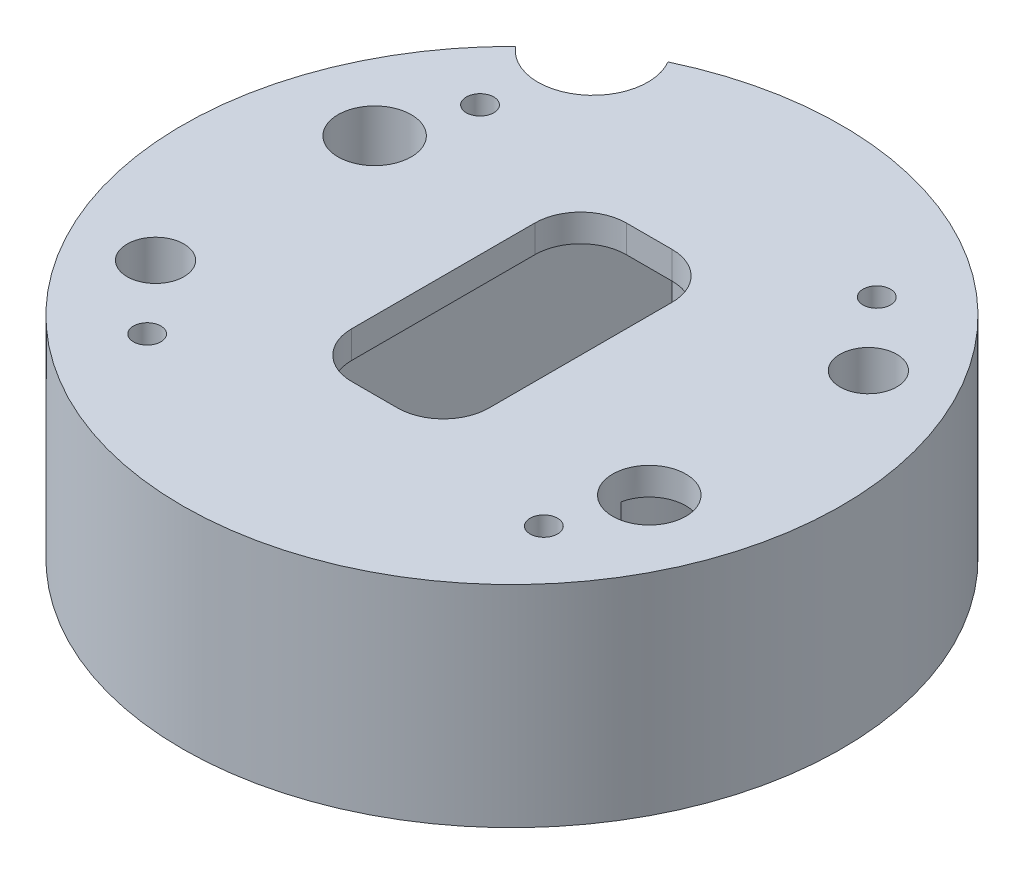
SolidWorks part; units mm, degrees
ref_plane "Front Plane" through (0, 0, 0) normal (0, 0, 1) x (1, 0, 0)
ref_plane "Top Plane" through (0, 0, 0) normal (0, 1, 0) x (1, 0, 0)
ref_plane "Right Plane" through (0, 0, 0) normal (1, 0, 0) x (0, 0, -1)
sketch "Sketch1" plane through (0, 0, 0) normal (0, 1, 0) x (1, 0, 0)
  line L0 (-13, 30.5) -> (13, -30.5) construction
  line L1 (-13, 30.5) -> (13, 30.5)
  line L2 (-13, 30.5) -> (-13, -30.5)
  line L3 (-13, -30.5) -> (13, -30.5)
  line L4 (13, 30.5) -> (13, -30.5)
  line L5 (-24.5, 0) -> (24.5, 0) construction
  line L6 (-34, 0) -> (-36, 0) construction
  line L7 (34, 0) -> (36, 0) construction
  line L8 (-15, 0) -> (-13, 0) construction
  circle A0 centre (0, 0) radius 36
  circle A3 centre (-24.5, 0) radius 9.5
  circle A4 centre (24.5, 0) radius 9.5
  point P5 (0, 0)
  point P12 (0, 0)
  dimension "D1" = 72
  dimension "D2" = 61
  dimension "D4" = 19
  dimension "D3" = 26
extrude "Boss-Extrude1" add sketch "Sketch1" along normal blind 20
sketch "Sketch4" plane through (0, 20, 0) normal (0, 1, 0) x (1, 0, 0)
  line L0 (-24.5, 9.5) -> (-24.5, 0) construction
  line L1 (-24.5, 0) -> (24.5, 0) construction
  line L2 (24.5, 0) -> (24.5, -9.5) construction
  line L3 (-24.5, 9.5) -> (-1.5428, 9.5) construction
  circle A0 centre (-24.5, 9.5) radius 4
  circle A1 centre (-24.5, 0) radius 9.5 construction
  circle A3 centre (24.5, -9.5) radius 4
  circle A5 centre (24.5, 0) radius 9.5 construction
  dimension "D1" = 8
extrude "Cut-Extrude6" cut sketch "Sketch4" against normal through all
sketch "Sketch5" plane through (0, 20, 0) normal (0, 1, 0) x (1, 0, 0)
  line L0 (0, 0) -> (20.0764, 0) construction
  line L1 (-18.1808, -21.667) -> (21.667, -18.1808) construction
  line L2 (-18.1808, -21.667) -> (-21.667, 18.1808) construction
  line L3 (-21.667, 18.1808) -> (18.1808, 21.667) construction
  line L4 (21.667, -18.1808) -> (18.1808, 21.667) construction
  line L5 (-18.1808, -21.667) -> (18.1808, 21.667) construction
  line L6 (-21.667, 18.1808) -> (21.667, -18.1808) construction
  circle A0 centre (-21.667, 18.1808) radius 1.5
  circle A1 centre (-18.1808, -21.667) radius 1.5
  circle A2 centre (21.667, -18.1808) radius 1.5
  circle A3 centre (18.1808, 21.667) radius 1.5
  circle A4 centre (-21.667, 18.1808) radius 2.3
  circle A5 centre (18.1808, 21.667) radius 2.3
  circle A6 centre (21.667, -18.1808) radius 2.3
  circle A7 centre (-18.1808, -21.667) radius 2.3
  point P0 (0, 0)
  dimension "D2" = 3
  dimension "D3" = 4.6
  dimension "D1" = 40
  dimension "D4" = 85
extrude "Cut-Extrude2" cut sketch "Sketch5" against normal blind 20 contours A0 | A3 | A1 | A2 region at (-21.667, 20, -18.1808) region at (-18.1808, 20, 21.667) region at (21.667, 20, 18.1808) region at (18.1808, 20, -21.667)
sketch "Sketch6" plane through (0, 20, 0) normal (0, 1, 0) x (1, 0, 0)
  line L0 (-24.6817, -14.25) -> (24.6817, 14.25) construction
  line L1 (0, 0) -> (24.909, 0) construction
  circle A0 centre (-24.6817, -14.25) radius 3.1
  circle A1 centre (24.6817, 14.25) radius 3.1
  point P4 (0, 0)
  dimension "D1" = 6.2
  dimension "D2" = 57
  dimension "D3" = 30
extrude "Cut-Extrude4" cut sketch "Sketch6" against normal through all both and the other way through all
sketch "Sketch7" plane through (0, 20, 0) normal (0, 1, 0) x (1, 0, 0)
  line L0 (-20.6488, 29.4895) -> (0, 0) construction
  line L1 (0, 0) -> (0, 21.7628) construction
  arc A0 (-25.2598, 25.6504) -> (-15.4641, 32.5094) centre (-20.6488, 29.4895) ccw
  circle A1 centre (0, 0) radius 36 construction
  arc A2 (-15.4641, 32.5094) -> (-25.2598, 25.6504) centre (0, 0) ccw
  dimension "D1" = 6
  dimension "D2" = 35
extrude "Cut-Extrude5" cut sketch "Sketch7" against normal through all both
sketch "Sketch9" plane through (0, 20, 0) normal (0, 1, 0) x (1, 0, 0)
  line L1 (-7.5, -15) -> (7.5, -15)
  line L2 (-7.5, -15) -> (-7.5, 15)
  line L3 (-7.5, 15) -> (7.5, 15)
  line L4 (-13, -30.5) -> (13, -30.5)
  line L5 (-13, 30.5) -> (-13, -30.5)
  line L6 (13, 30.5) -> (-13, 30.5)
  line L7 (13, -30.5) -> (13, 30.5)
  line L8 (-13, -30.5) -> (13, -30.5)
  line L9 (-13, 30.5) -> (-13, -30.5)
  line L10 (13, 30.5) -> (-13, 30.5)
  line L11 (13, -30.5) -> (13, 30.5)
  line L12 (7.5, -15) -> (7.5, 15)
  line L13 (-7.5, -15) -> (7.5, 15) construction
  line L14 (-7.5, 15) -> (7.5, -15) construction
  arc A0 (-28.4104, 8.6579) -> (-20.5896, 8.6579) centre (-24.5, 9.5) ccw
  circle A1 centre (21.667, -18.1808) radius 1.5
  arc A2 (20.5896, -8.6579) -> (28.4104, -8.6579) centre (24.5, -9.5) ccw
  arc A3 (28.4104, -8.6579) -> (20.5896, -8.6579) centre (24.5, 0) ccw
  arc A4 (20.5896, -8.6579) -> (28.4104, -8.6579) centre (24.5, -9.5) ccw
  arc A5 (28.4104, -8.6579) -> (20.5896, -8.6579) centre (24.5, 0) ccw
  arc A6 (-20.5896, 8.6579) -> (-28.4104, 8.6579) centre (-24.5, 9.5) ccw
  arc A7 (-28.4104, 8.6579) -> (-20.5896, 8.6579) centre (-24.5, 0) ccw
  arc A8 (-20.5896, 8.6579) -> (-28.4104, 8.6579) centre (-24.5, 9.5) ccw
  arc A9 (-28.4104, 8.6579) -> (-20.5896, 8.6579) centre (-24.5, 0) ccw
  circle A10 centre (21.667, -18.1808) radius 1.5
  circle A11 centre (-18.1808, -21.667) radius 1.5
  circle A12 centre (-18.1808, -21.667) radius 1.5
  circle A13 centre (18.1808, 21.667) radius 1.5
  circle A14 centre (18.1808, 21.667) radius 1.5
  circle A15 centre (-21.667, 18.1808) radius 1.5
  circle A16 centre (-21.667, 18.1808) radius 1.5
  circle A17 centre (24.6817, 14.25) radius 3.1
  circle A18 centre (24.6817, 14.25) radius 3.1
  circle A19 centre (-24.6817, -14.25) radius 3.1
  circle A20 centre (-24.6817, -14.25) radius 3.1
  arc A21 (28.4104, -8.6579) -> (20.5896, -8.6579) centre (24.5, -9.5) ccw
  arc A22 (-25.2598, 25.6504) -> (-15.4641, 32.5094) centre (-20.6488, 29.4895) ccw
  arc A23 (-25.2598, 25.6504) -> (-15.4641, 32.5094) centre (0, 0) ccw
  arc A24 (-25.2598, 25.6504) -> (-15.4641, 32.5094) centre (-20.6488, 29.4895) ccw
  arc A25 (-25.2598, 25.6504) -> (-15.4641, 32.5094) centre (0, 0) ccw
  arc M17 (-15.4641, 32.5094) -> (-25.2598, 25.6504) centre (-20.6488, 29.4895) cw
  arc M18 (-25.2598, 25.6504) -> (-15.4641, 32.5094) centre (0, 0) ccw
  circle M19 centre (-24.6817, -14.25) radius 3.1
  circle M20 centre (24.6817, 14.25) radius 3.1
  circle M21 centre (-21.667, 18.1808) radius 1.5
  circle M22 centre (18.1808, 21.667) radius 1.5
  circle M23 centre (-18.1808, -21.667) radius 1.5
  circle M24 centre (21.667, -18.1808) radius 1.5
  arc M25 (-28.4104, 8.6579) -> (-20.5896, 8.6579) centre (-24.5, 9.5) cw
  arc M26 (-20.5896, 8.6579) -> (-28.4104, 8.6579) centre (-24.5, 0) cw
  arc M27 (28.4104, -8.6579) -> (20.5896, -8.6579) centre (24.5, -9.5) cw
  arc M28 (20.5896, -8.6579) -> (28.4104, -8.6579) centre (24.5, 0) cw
  line M29 (13, -30.5) -> (-13, -30.5)
  line M30 (-13, -30.5) -> (-13, 30.5)
  line M31 (-13, 30.5) -> (13, 30.5)
  line M32 (13, 30.5) -> (13, -30.5)
  dimension "D11" = 15
  dimension "D12" = 30
  dimension "D1" = 0
  dimension "D2" = 0
  dimension "D3" = 0
  dimension "D4" = 0
  dimension "D5" = 0
  dimension "D6" = 0
  dimension "D7" = 0
  dimension "D8" = 0
  dimension "D9" = 0
  dimension "D10" = 0
extrude "Boss-Extrude2" add sketch "Sketch9" along normal blind 3 contours M18 M17 M19 M21 M23 M26 M25 M28 M27 M32 M29 M30 M31 M24 M22 M20 | A0 M26 | A21 M28 | M29 M32 M31 M30 region at (-12.3369, 20, 0) region at (-24.5, 20, 0.6723) region at (24.5, 20, -0.6723) region at (-16.6233, 20, -23.7405)
fillet "Fillet1" radius 5 4 edges at (7.5, 21.5, 15) (-7.5, 21.5, 15) (-7.5, 21.5, -15) (7.5, 21.5, -15)
